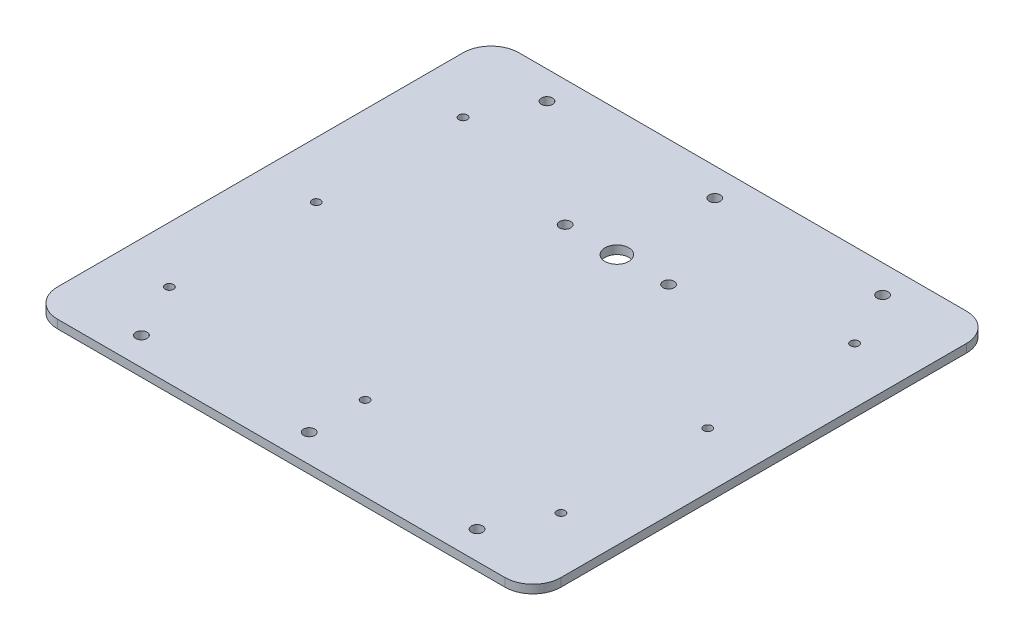
SolidWorks part; units mm, degrees
material "1060 合金"
ref_plane "前视基准面" through (0, 0, 0) normal (0, 0, 1) x (1, 0, 0)
ref_plane "上视基准面" through (0, 0, 0) normal (0, 1, 0) x (1, 0, 0)
ref_plane "右视基准面" through (0, 0, 0) normal (1, 0, 0) x (0, 0, -1)
sketch "草图1" plane through (0, 0, 0) normal (0, 1, 0) x (1, 0, 0)
  line L1 (-80, 82.5) -> (80, 82.5)
  line L2 (-90, 72.5) -> (-90, -72.5)
  line L3 (-80, -82.5) -> (80, -82.5)
  line L4 (90, 72.5) -> (90, -72.5)
  line L5 (-90, 82.5) -> (90, -82.5) construction
  line L6 (-90, -82.5) -> (90, 82.5) construction
  arc A0 (-90, -72.5) -> (-80, -82.5) centre (-80, -72.5) ccw
  arc A1 (80, -82.5) -> (90, -72.5) centre (80, -72.5) ccw
  arc A2 (80, 82.5) -> (90, 72.5) centre (80, 72.5) cw
  arc A3 (-80, 82.5) -> (-90, 72.5) centre (-80, 72.5) ccw
  circle A4 centre (0, 72.5) radius 2
  circle A5 centre (60, 72.5) radius 2
  circle A6 centre (-60, 72.5) radius 2
  circle A7 centre (0, -72.5) radius 2
  circle A8 centre (-60, -72.5) radius 2
  circle A9 centre (60, -72.5) radius 2
  circle A10 centre (0, 37.5) radius 4.25
  circle A11 centre (18.5, 37.5) radius 2
  circle A12 centre (-18.5, 37.5) radius 2
  circle A13 centre (70, 52.5) radius 1.5
  circle A14 centre (70, 0) radius 1.5
  circle A15 centre (70, -52.5) radius 1.5
  circle A16 centre (-70, 52.5) radius 1.5
  circle A17 centre (-70, 0) radius 1.5
  circle A18 centre (-70, -52.5) radius 1.5
  circle A19 centre (0, -52.5) radius 1.5
  point P1 (0, 0)
  dimension "D3" = 10
  dimension "D4" = 4
  dimension "D5" = 4
  dimension "D6" = 4
  dimension "D9" = 10
  dimension "D10" = 60
  dimension "D11" = 60
  dimension "D12" = 90
  dimension "D13" = 4
  dimension "D14" = 4
  dimension "D15" = 4
  dimension "D16" = 60
  dimension "D17" = 60
  dimension "D18" = 90
  dimension "D19" = 10
  dimension "D20" = 10
  dimension "D21" = 10
  dimension "D22" = 8.5
  dimension "D23" = 90
  dimension "D24" = 45
  dimension "D25" = 4
  dimension "D26" = 4
  dimension "D27" = 18.5
  dimension "D28" = 18.5
  dimension "D31" = 3
  dimension "D32" = 20
  dimension "D33" = 30
  dimension "D34" = 3
  dimension "D35" = 20
  dimension "D37" = 20
  dimension "D38" = 3
  dimension "D39" = 30
  dimension "D40" = 3
  dimension "D41" = 3
  dimension "D42" = 3
  dimension "D43" = 20
  dimension "D44" = 20
  dimension "D45" = 20
  dimension "D46" = 30
  dimension "D47" = 82.5
  dimension "D49" = 3
  dimension "D50" = 30
  dimension "D51" = 90
  dimension "D1" = 180
  dimension "D2" = 165
  dimension "D7" = 10
  dimension "D8" = 10
  dimension "D29" = 18.5
  dimension "D30" = 18.5
  dimension "D36" = 82.5
  dimension "D48" = 30
base flange "基体-法兰1" sketch "草图1" thickness 3 reverse thickness direction no parameters "D1"=0.7366
sketch "折弯-线1" [suppressed] plane through (0, 0, 0) normal (0, 1, 0) x (1, 0, 0)
sketch "边界框1" [suppressed] plane through (0, 0, 0) normal (0, 1, 0) x (1, 0, 0)
sheet metal parameters "钣金6" thickness 3 parameters "D1"=0.7366
flat pattern "平板型式6" [suppressed]
sketch "折弯-线2" plane through (0, 0, 0) normal (0, 1, 0) x (1, 0, 0)
sketch3d "边界框2" [suppressed]
  line L0 (170, -10, 0) -> (-10, -10, 0) construction
  line L1 (170, 155, 0) -> (-10, 155, 0) construction
  line L2 (170, -10, 0) -> (170, 155, 0) construction
  line L3 (-10, -10, 0) -> (-10, 155, 0) construction
